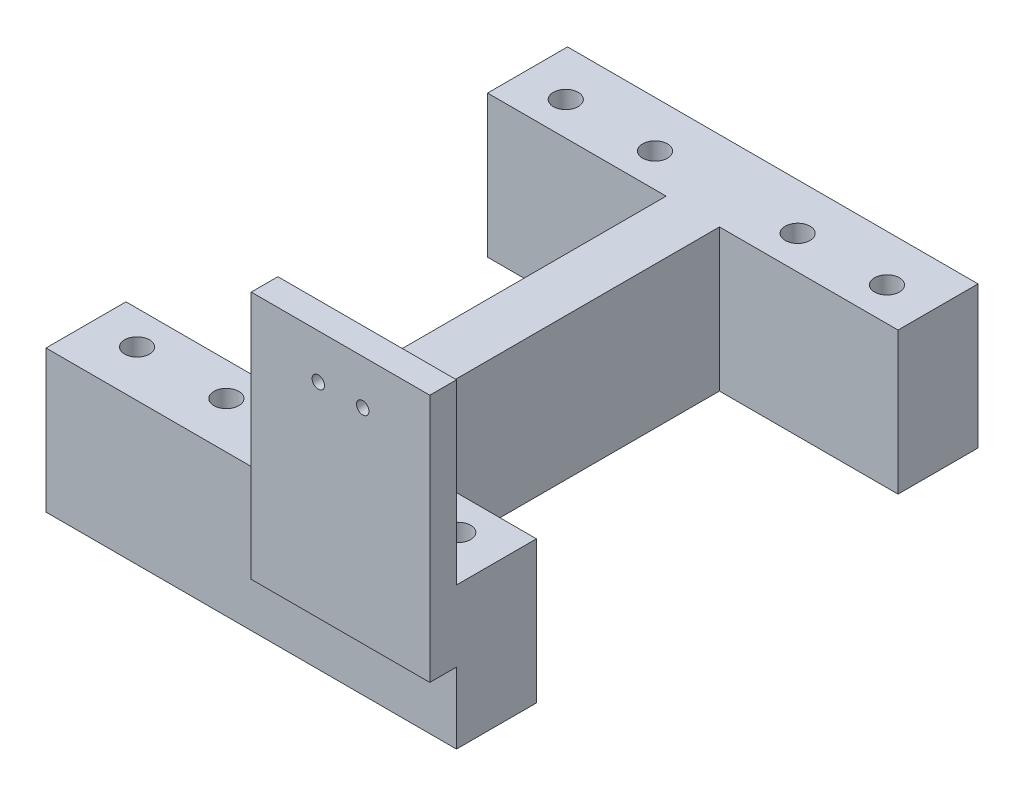
SolidWorks part; units mm, degrees
ref_plane "Front" through (0, 0, 0) normal (0, 0, 1) x (1, 0, 0)
ref_plane "Top" through (0, 0, 0) normal (0, 1, 0) x (1, 0, 0)
ref_plane "Right" through (0, 0, 0) normal (1, 0, 0) x (0, 0, -1)
sketch "Эскиз1" plane through (0, 0, 0) normal (0, 1, 0) x (1, 0, 0)
  line L0 (0, 20.35) -> (0, -20.35) construction
  line L1 (-22.3672, 0) -> (21.2348, 0) construction
  line L2 (0, -20.35) -> (0, -29.35) construction
  line L3 (-10.05, -20.35) -> (10.05, -20.35)
  line L4 (-10.05, -20.35) -> (-10.05, 20.35)
  line L5 (-10.05, 20.35) -> (10.05, 20.35)
  line L6 (10.05, -20.35) -> (10.05, 20.35)
  line L7 (-10.05, -20.35) -> (10.05, 20.35) construction
  line L8 (-10.05, 20.35) -> (10.05, -20.35) construction
  line L9 (10.05, -20.35) -> (-10.05, -20.35)
  line L10 (10.05, -20.35) -> (10.05, -29.35)
  line L11 (10.05, -29.35) -> (-10.05, -29.35)
  line L12 (-10.05, -20.35) -> (-10.05, -29.35)
  line L13 (10.05, 20.35) -> (-10.05, 20.35)
  line L14 (10.05, 20.35) -> (10.05, 29.35)
  line L15 (10.05, 29.35) -> (-10.05, 29.35)
  line L16 (-10.05, 20.35) -> (-10.05, 29.35)
  line L17 (0, 20.35) -> (0, 29.35) construction
  line L18 (10.05, -24.125) -> (5.025, -24.125) construction
  line L19 (5.025, -24.125) -> (-5.025, -24.125) construction
  line L20 (-5.025, -24.125) -> (-10.05, -24.125) construction
  line L21 (-10.05, 24.85) -> (-5.025, 24.125) construction
  line L22 (-5.025, 24.125) -> (5.025, 24.125) construction
  line L23 (5.025, 24.125) -> (10.05, 24.85) construction
  line L24 (-13.05, -28.75) -> (-13.05, 28.75) construction
  line L25 (-31.125, 24.125) -> (-36.15, 24.85) construction
  line L26 (-21.075, 24.125) -> (-31.125, 24.125) construction
  line L27 (-16.05, 24.85) -> (-21.075, 24.125) construction
  line L28 (-21.075, -24.125) -> (-16.05, -24.125) construction
  line L29 (-31.125, -24.125) -> (-21.075, -24.125) construction
  line L30 (-36.15, -24.125) -> (-31.125, -24.125) construction
  line L31 (-26.1, 20.35) -> (-26.1, 29.35) construction
  line L32 (-16.05, 20.35) -> (-36.15, -20.35) construction
  line L33 (-16.05, -20.35) -> (-36.15, 20.35) construction
  line L34 (-26.1, -20.35) -> (-26.1, -29.35) construction
  line L35 (-26.1, 20.35) -> (-26.1, -20.35) construction
  line L36 (-16.05, 20.35) -> (-16.05, 29.35)
  line L37 (-36.15, 29.35) -> (-16.05, 29.35)
  line L38 (-36.15, 20.35) -> (-36.15, 29.35)
  line L39 (-36.15, 20.35) -> (-16.05, 20.35)
  line L40 (-16.05, -20.35) -> (-16.05, -29.35)
  line L41 (-36.15, -29.35) -> (-16.05, -29.35)
  line L42 (-36.15, -20.35) -> (-36.15, -29.35)
  line L43 (-36.15, -20.35) -> (-16.05, -20.35)
  line L44 (-36.15, -20.35) -> (-36.15, 20.35)
  line L45 (-16.05, 20.35) -> (-36.15, 20.35)
  line L46 (-16.05, -20.35) -> (-16.05, 20.35)
  line L47 (-16.05, -20.35) -> (-36.15, -20.35)
  line L48 (-16.05, -29.35) -> (-10.05, -29.35)
  line L49 (-16.05, 29.35) -> (-10.05, 29.35)
  line L50 (-10.05, -29.35) -> (-10.05, -32.35)
  line L51 (-10.05, -32.35) -> (10.05, -32.35)
  line L52 (10.05, -32.35) -> (10.05, -29.35)
  circle A0 centre (5.025, -24.125) radius 1.4
  circle A1 centre (-5.025, -24.125) radius 1.4
  circle A2 centre (-5.025, 24.125) radius 1.4
  circle A3 centre (5.025, 24.125) radius 1.4
  circle A4 centre (-31.125, 24.125) radius 1.4
  circle A5 centre (-21.075, 24.125) radius 1.4
  circle A6 centre (-21.075, -24.125) radius 1.4
  circle A7 centre (-31.125, -24.125) radius 1.4
  ellipse E0 centre (10.05, 0) end of major axis (10.05, -29.35) minor radius 7.2824 (10.05, 29.35) -> (10.05, -29.35) cw
  ellipse E1 centre (-36.15, 0) end of major axis (-36.15, -29.35) minor radius 7.2824 (-36.15, 29.35) -> (-36.15, -29.35) ccw
  point P5 (0, 0)
  point P54 (-26.1, 0)
  point P55 (10.05, 0)
  dimension "D3" = 2.8
  dimension "D1" = 40.7
  dimension "D2" = 20.1
  dimension "D4" = 10.05
  dimension "D5" = 48.25
  dimension "D6" = 9
  dimension "D7" = 3
  dimension "D8" = 3
extrude "Бобышка-Вытянуть2" add sketch "Эскиз1" along normal blind 8 and the other way blind 8 contours L43 L42 L41 L40 A6 A7 | L49 L36 L46 L40 L48 L12 L4 L16 | L3 L12 L11 L10 A0 A1 | L16 L5 L14 L15 A2 A3 | L38 L39 L36 L37 A4 A5 region at (-13.05, 0, 0) region at (0, 0, 24.903) region at (0, 0, -24.903) region at (-26.1, 0, 24.903) region at (-26.1, 0, -24.903)
extrude "Бобышка-Вытянуть3" add sketch "Эскиз1<4>" along normal blind 28 contours L51 L52 L11 L50 region at (0, 0, 30.85)
sketch "Эскиз1<4>" plane through (0, 0, 0) normal (0, 1, 0) x (1, 0, 0) same geometry as "Эскиз1"
sketch "Эскиз3" plane through (0, 0, 29.35) normal (0, 0, -1) x (-1, 0, 0)
  line L3 (-6.942, 23) -> (0, 23) construction
  line L7 (0, 23) -> (5.7795, 23) construction
  circle A0 centre (-2.5, 23) radius 0.7
  circle A1 centre (2.5, 23) radius 0.7
  dimension "D2" = 5
  dimension "D3" = 1.4
  dimension "D4" = 1.4
extrude "Вырез-Вытянуть1" cut sketch "Эскиз3" against normal blind 28
